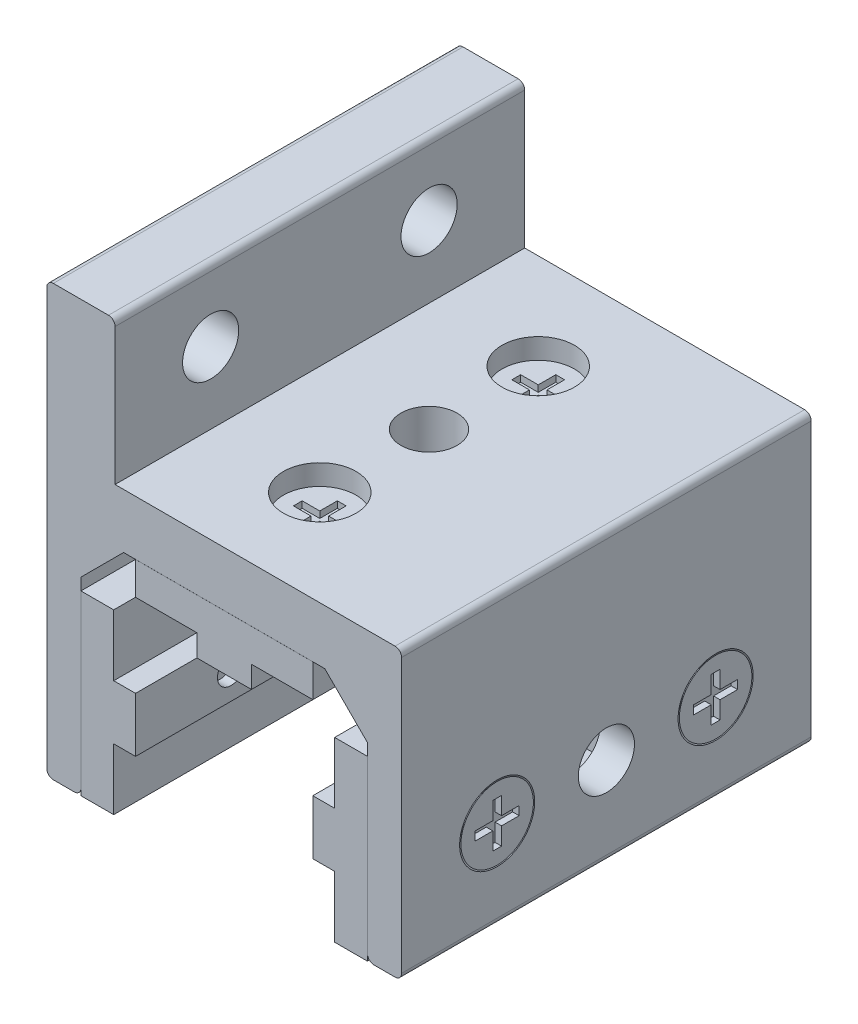
SolidWorks part; units mm, degrees
ref_plane "Front Plane" through (0, 0, 0) normal (0, 0, 1) x (1, 0, 0)
ref_plane "Top Plane" through (0, 0, 0) normal (0, 1, 0) x (1, 0, 0)
ref_plane "Right Plane" through (0, 0, 0) normal (1, 0, 0) x (0, 0, -1)
sketch "Sketch1" plane through (0, 0, 0) normal (0, 0, 1) x (1, 0, 0)
  line L0 (0, -24.9936) -> (0, 24.9936) construction
  line L1 (-20.6248, 0) -> (20.6248, 0) construction
  line L2 (-20.6248, 24.9936) -> (-20.6248, -24.9936) construction
  line L3 (-20.6248, -24.9936) -> (-16.656, -24.9936) construction
  line L4 (-16.656, -24.9936) -> (-16.656, -2.9797) construction
  line L5 (-16.656, -2.9797) -> (-11.6951, 1.9812) construction
  line L6 (-11.6951, 1.9812) -> (11.6951, 1.9812) construction
  line L7 (11.6951, 1.9812) -> (16.656, -2.9797) construction
  line L8 (16.656, -2.9797) -> (16.6561, -24.9936) construction
  line L9 (16.6561, -24.9936) -> (20.6248, -24.9936) construction
  line L10 (20.6248, -24.9936) -> (20.6248, 8.3312) construction
  line L11 (20.6248, 8.3312) -> (-12.6873, 8.3312) construction
  line L12 (-12.6873, 8.3312) -> (-12.6873, 24.9936) construction
  line L13 (-12.6873, 24.9936) -> (-20.6248, 24.9936) construction
  line L14 (-16.6561, -4.3688) -> (-12.8461, -4.3688) construction
  line L15 (-12.8461, -4.3688) -> (-12.8461, -11.5062) construction
  line L16 (-12.8461, -11.5062) -> (-10.306, -11.5062) construction
  line L17 (-10.306, -11.5062) -> (-10.306, -17.8562) construction
  line L18 (-10.306, -17.8562) -> (-12.8461, -17.8562) construction
  line L19 (-12.8461, -17.8562) -> (-12.8461, -24.9936) construction
  line L20 (-12.8461, -24.9936) -> (-16.656, -24.9936) construction
  line L21 (-12.8461, -11.5062) -> (-12.8461, -17.8562) construction
  line L22 (-10.306, -14.6812) -> (-16.656, -14.6812) construction
  line L23 (-16.656, -14.6812) -> (20.6248, -14.6812) construction
  point P4 (0, 0)
  point P7 (0, 0)
  point P30 (0, 1.9812)
  point P31 (0, 5.1562)
  dimension "Length (B)" = 49.9872
  dimension "Length (A)" = 41.2496
  dimension "Mounting Hole Depth" = 7.9375
  dimension "D1" = 3.9688
  dimension "Chamfer" = 4.9609
  dimension "D2" = 45
  dimension "Pad Width" = 20.6248
  dimension "Pad Height" = 6.35
  dimension "Pad Thickness" = 3.81
  dimension "Pad Rail" = 6.35
  dimension "Countersink Depth" = 3.175
  dimension "Inner Height" = 26.9748
  dimension "Length (C)" = 33.3248
sketch "Sketch2" plane through (0, 0, 0) normal (1, 0, 0) x (0, 0, -1)
  line L0 (-23.8125, 0) -> (23.8125, 0) construction
  line L1 (-23.8125, 8.3312) -> (23.8125, 8.3312) construction
  line L2 (-23.8125, 24.9936) -> (23.8125, 24.9936) construction
  line L3 (-23.8125, 24.9936) -> (-23.8125, -24.9936) construction
  line L4 (-23.8125, -24.9936) -> (23.8125, -24.9936) construction
  line L5 (23.8125, 24.9936) -> (23.8125, -24.9936) construction
  line L7 (0, 24.9936) -> (0, 8.3312) construction
  line L8 (-12.7, 16.6624) -> (12.7, 16.6624) construction
  line L9 (-23.8125, -14.6812) -> (23.8125, -14.6812) construction
  line L10 (-13.2105, -17.2339) -> (-12.1895, -17.2339) construction
  line L11 (-13.2105, -17.2339) -> (-13.2105, -12.1285) construction
  line L12 (-13.2105, -12.1285) -> (-12.1895, -12.1285) construction
  line L13 (-12.1895, -17.2339) -> (-12.1895, -12.1285) construction
  line L14 (-12.7, -12.1285) -> (-12.7, -17.2339) construction
  line L15 (-13.2105, -14.6812) -> (-12.1895, -14.6812) construction
  line L16 (-15.2527, -14.1707) -> (-10.1473, -14.1707) construction
  line L17 (-15.2527, -14.1707) -> (-15.2527, -15.1917) construction
  line L18 (-15.2527, -15.1917) -> (-10.1473, -15.1917) construction
  line L19 (-10.1473, -14.1707) -> (-10.1473, -15.1917) construction
  line L20 (-12.7, -15.1917) -> (-12.7, -14.1707) construction
  line L21 (-15.2527, -14.6812) -> (-10.1473, -14.6812) construction
  line L22 (12.7, -12.1285) -> (-12.7, -12.1285) construction
  line L23 (0, -14.6812) -> (0, -12.1285) construction
  circle A0 centre (-12.7, 16.6624) radius 3.2639 construction
  circle A1 centre (12.7, 16.6624) radius 3.2639 construction
  circle A2 centre (0, -14.6812) radius 3.2639 construction
  circle A3 centre (-12.7, -14.6812) radius 2.5527 construction
  circle A4 centre (12.7, -14.6812) radius 2.5527 construction
  circle A5 centre (12.7, -14.6812) radius 1.5875
  circle A6 centre (-12.7, -14.6812) radius 1.5875
  point P12 (0, 8.3312)
  point P16 (0, 16.6624)
  point P22 (0, -14.6812)
  point P42 (0, -14.6812)
  point P44 (0, 16.6624)
  dimension "Mounting Hole Diameter" = 6.5278
  dimension "Hole Diameter 2" = 6.5278
  dimension "D1" = 5.1054
  dimension "Pilot Hole" = 3.175
  dimension "Length" = 47.625
  dimension "Mounting Hole Spacing" = 25.4
  dimension "D2" = 1.0211
sketch "Sketch3" plane through (0, 0, 0) normal (0, 1, 0) x (1, 0, 0)
  line L0 (0, -23.8125) -> (0, 23.8125) construction
  line L1 (0, 12.7) -> (0, -12.7) construction
  line L5 (0, -23.8125) -> (0, 23.8125) construction
  circle A0 centre (0, 12.7) radius 2.5527 construction
  circle A1 centre (0, -12.7) radius 2.5527 construction
  circle A2 centre (0, 0) radius 3.2639 construction
  circle A3 centre (0, 12.7) radius 4.2164 construction
  circle A4 centre (0, -12.7) radius 4.2164 construction
  dimension "D1" = 6.5278
  dimension "D2" = 5.1054
  dimension "Countersink Diameter" = 8.4328
ref_plane "Plane1" through (0, 0, 12.7) normal (0, 0, 1) x (1, 0, 0)
sketch "Sketch11" plane through (0, 0, 12.7) normal (0, 0, 1) x (1, 0, 0)
  line L0 (-16.656, -14.6812) -> (-20.6248, -14.6812) construction
  line L1 (-20.6248, 24.9936) -> (-20.6248, -24.9936) construction
  line L2 (-20.6248, -10.4648) -> (-20.6248, -18.8976) construction
  line L3 (-20.6248, -10.4648) -> (-19.1116, -12.2682) construction
  line L4 (-19.1116, -12.2682) -> (-19.1116, -17.0942) construction
  line L5 (-19.1116, -17.0942) -> (-20.6248, -18.8976) construction
  line L6 (-19.1116, -12.2682) -> (-11.5761, -12.2682) construction
  line L7 (-11.5761, -12.2682) -> (-11.5761, -11.5062) construction
  line L8 (-12.8461, -11.5062) -> (-10.306, -11.5062) construction
  point P7 (-19.8682, -11.3665)
  dimension "D1" = 8.4328
  dimension "D2" = 100
  dimension "D3" = 4.826
sketch "Sketch4" plane through (0, 0, 0) normal (0, 0, 1) x (1, 0, 0)
  line L0 (-20.6248, -24.9936) -> (-16.656, -24.9936) construction
  line L1 (-20.6248, 24.9936) -> (-20.6248, -24.9936) construction
  line L2 (-12.6873, 24.9936) -> (-20.6248, 24.9936) construction
  line L3 (-12.6873, 8.3312) -> (-12.6873, 24.9936) construction
  line L4 (20.6248, 8.3312) -> (-12.6873, 8.3312) construction
  line L5 (20.6248, -24.9936) -> (20.6248, 8.3312) construction
  line L6 (16.6561, -24.9936) -> (20.6248, -24.9936) construction
  line L7 (16.656, -2.9797) -> (16.6561, -24.9936) construction
  line L8 (11.6951, 1.9812) -> (16.656, -2.9797) construction
  line L9 (-11.6951, 1.9812) -> (11.6951, 1.9812) construction
  line L10 (-16.656, -2.9797) -> (-11.6951, 1.9812) construction
  line L11 (-16.656, -24.9936) -> (-16.656, -2.9797) construction
  line L12 (-20.6248, -24.9936) -> (-16.656, -24.9936)
  line L13 (-20.6248, 24.9936) -> (-20.6248, -24.9936)
  line L14 (-12.6873, 24.9936) -> (-20.6248, 24.9936)
  line L15 (-12.6873, 8.3312) -> (-12.6873, 24.9936)
  line L16 (20.6248, 8.3312) -> (-12.6873, 8.3312)
  line L17 (20.6248, -24.9936) -> (20.6248, 8.3312)
  line L18 (16.6561, -24.9936) -> (20.6248, -24.9936)
  line L19 (16.656, -2.9797) -> (16.6561, -24.9936)
  line L20 (11.6951, 1.9812) -> (16.656, -2.9797)
  line L21 (-11.6951, 1.9812) -> (11.6951, 1.9812)
  line L22 (-16.656, -2.9797) -> (-11.6951, 1.9812)
  line L23 (-16.656, -24.9936) -> (-16.656, -2.9797)
extrude "Boss-Extrude1" add sketch "Sketch4" along normal up to vertex (23.8125 mm away) and the other way up to vertex (23.8125 mm away) up to point (0, -24.9936, 23.8125) other way up to point (0, 8.3312, -23.8125)
sketch "Sketch5" plane through (0, 0, 0) normal (0, 0, 1) x (1, 0, 0)
  line L0 (-16.6561, -4.3688) -> (-16.656, -24.9936)
  line L1 (-16.656, -24.9936) -> (-12.8461, -24.9936)
  line L2 (-12.8461, -24.9936) -> (-12.8461, -17.8562)
  line L3 (-12.8461, -17.8562) -> (-10.306, -17.8562)
  line L4 (-10.306, -17.8562) -> (-10.306, -11.5062)
  line L5 (-10.306, -11.5062) -> (-12.8461, -11.5062)
  line L6 (-12.8461, -11.5062) -> (-12.8461, -4.3688)
  line L7 (-12.8461, -4.3688) -> (-16.6561, -4.3688)
extrude "Boss-Extrude2" add sketch "Sketch5" along normal up to surface and the other way up to surface from offset 1.7272 separate body
sketch "Sketch6" plane through (0, 0, 0) normal (1, 0, 0) x (0, 0, -1)
  circle A0 centre (-12.7, -14.6812) radius 2.5527 construction
  circle A1 centre (0, -14.6812) radius 3.2639 construction
  circle A2 centre (12.7, -14.6812) radius 2.5527 construction
  circle A3 centre (12.7, 16.6624) radius 3.2639 construction
  circle A4 centre (-12.7, 16.6624) radius 3.2639 construction
  circle A5 centre (-12.7, -14.6812) radius 2.5527
  circle A6 centre (0, -14.6812) radius 3.2639
  circle A7 centre (12.7, -14.6812) radius 2.5527
  circle A8 centre (12.7, 16.6624) radius 3.2639
  circle A9 centre (-12.7, 16.6624) radius 3.2639
  point P15 (-12.7, 16.6624)
extrude "Cut-Extrude1" cut sketch "Sketch6" against normal through all both and the other way through all
sketch "Sketch7" plane through (0, 0, 0) normal (1, 0, 0) x (0, 0, -1)
  line L1 (-3.2639, -17.9451) -> (3.2639, -17.9451)
  line L2 (-3.2639, -17.9451) -> (-3.2639, -11.4173)
  line L3 (-3.2639, -11.4173) -> (3.2639, -11.4173)
  line L4 (3.2639, -17.9451) -> (3.2639, -11.4173)
  line L5 (0, -11.4173) -> (0, -17.9451) construction
  line L6 (-3.2639, -14.6812) -> (3.2639, -14.6812) construction
  circle A0 centre (-12.7, -14.6812) radius 1.5875 construction
  circle A1 centre (-12.7, -14.6812) radius 1.5875
  circle A2 centre (12.7, -14.6812) radius 1.5875 construction
  circle A3 centre (12.7, -14.6812) radius 1.5875
  circle A4 centre (0, -14.6812) radius 3.2639 construction
  point P6 (0, -14.6812)
extrude "Cut-Extrude2" cut sketch "Sketch7" against normal through all
sketch "Sketch8" plane through (0, 8.3312, 0) normal (0, 1, 0) x (1, 0, 0)
  circle A0 centre (0, 12.7) radius 2.5527 construction
  circle A1 centre (0, -12.7) radius 2.5527 construction
  circle A2 centre (0, 12.7) radius 2.5527
  circle A3 centre (0, -12.7) radius 2.5527
extrude "Cut-Extrude3" cut sketch "Sketch8" against normal up to vertex (6.35 mm away) up to point (0, 1.9812, 0)
sketch "Sketch9" plane through (0, 8.3312, 0) normal (0, 1, 0) x (1, 0, 0)
  circle A0 centre (0, 12.7) radius 4.2164 construction
  circle A1 centre (0, 12.7) radius 4.2164
  circle A2 centre (0, -12.7) radius 4.2164 construction
  circle A3 centre (0, -12.7) radius 4.2164
extrude "Cut-Extrude4" cut sketch "Sketch9" against normal up to vertex (3.175 mm away) up to point (0, 5.1562, 0)
chamfer "Chamfer1" distance 1.524 angle 50 6 edges at (-20.6248, -14.6812, -15.2527) (-20.6248, -14.6812, 10.1473) (20.6248, -14.6812, -15.2527) (20.6248, -14.6812, 10.1473) (-2.5527, 5.1562, 12.7) (-2.5527, 5.1562, -12.7)
sketch "Sketch12" plane through (0, 0, 12.7) normal (0, 0, 1) x (1, 0, 0)
  line L0 (-20.6248, -10.4648) -> (-20.6248, -14.6812)
  line L1 (-20.6248, -14.6812) -> (-11.5761, -14.6812)
  line L2 (-11.5761, -14.6812) -> (-11.5761, -12.2682)
  line L3 (-11.5761, -12.2682) -> (-19.1116, -12.2682)
  line L4 (-19.1116, -12.2682) -> (-20.6248, -10.4648)
revolve "Revolve1" add sketch "Sketch12" angle 360 about L1
sketch "Sketch13" plane through (-20.6248, 0, 0) normal (-1, 0, 0) x (0, 0, 1)
  line L0 (13.2105, -17.2339) -> (12.1895, -17.2339) construction
  line L1 (13.2105, -17.2339) -> (13.2105, -12.1285) construction
  line L2 (13.2105, -12.1285) -> (12.1895, -12.1285) construction
  line L3 (12.1895, -17.2339) -> (12.1895, -12.1285) construction
  line L4 (13.2105, -17.2339) -> (12.1895, -17.2339)
  line L5 (13.2105, -17.2339) -> (13.2105, -15.1917)
  line L6 (13.2105, -12.1285) -> (12.1895, -12.1285)
  line L7 (12.1895, -17.2339) -> (12.1895, -15.1917)
  line L8 (15.2527, -14.1707) -> (15.2527, -15.1917) construction
  line L9 (15.2527, -15.1917) -> (10.1473, -15.1917) construction
  line L10 (10.1473, -14.1707) -> (10.1473, -15.1917) construction
  line L11 (15.2527, -14.1707) -> (10.1473, -14.1707) construction
  line L12 (15.2527, -14.1707) -> (15.2527, -15.1917)
  line L13 (15.2527, -15.1917) -> (13.2105, -15.1917)
  line L14 (10.1473, -14.1707) -> (10.1473, -15.1917)
  line L15 (15.2527, -14.1707) -> (13.2105, -14.1707)
  line L16 (12.1895, -14.1707) -> (10.1473, -14.1707)
  line L17 (12.1895, -14.1707) -> (12.1895, -12.1285)
  line L18 (12.1895, -15.1917) -> (10.1473, -15.1917)
  line L19 (13.2105, -14.1707) -> (13.2105, -12.1285)
extrude "Cut-Extrude5" cut sketch "Sketch13" against normal up to vertex (0.7566 mm away) up to point (-19.8682, -11.3665, 12.7)
pattern_linear "LPattern1" count 2 spacing 25.4 along (0, 0, -1) of bodies 111
pattern_circular "CirPattern1" count 3 over 180 about axis through (0, -14.6812, 0) along (0, 0, 1) of bodies 107 111 112
fillet "Fillet1" radius 0.762 7 edges at (-12.6873, 24.9936, 0) (-20.6248, 24.9936, 0) (20.6248, 8.3312, 0) (20.6248, -24.9936, 0) (16.6561, -24.9936, 0) (-16.656, -24.9936, 0) (-20.6248, -24.9936, 0)
sketch "Sketch14" plane through (0, 8.3312, 0) normal (0, 1, 0) x (1, 0, 0)
  circle A0 centre (0, 0) radius 3.2639
  circle A1 centre (0, 0) radius 3.2639 construction
extrude "Cut-Extrude6" cut sketch "Sketch14" against normal through all
equation "\"D1@Sketch1\" = \"Mounting Hole Depth@Sketch1\" / 2"
equation "\"D1@Sketch3\"=\"Hole Diameter 2@Sketch2\""
equation "\"D2@Sketch3\"=\"D1@Sketch2\""
equation "\"D2@Sketch2\"=\"D1@Sketch2\"*.2"
equation "\"D1@Sketch11\"=\"Countersink Diameter@Sketch3\""
equation "\"D3@LPattern1\"=\"Mounting Hole Spacing@Sketch2\""
equation "\"Chamfer@Sketch1\"=\"Mounting Hole Depth@Sketch1\"*.625"
